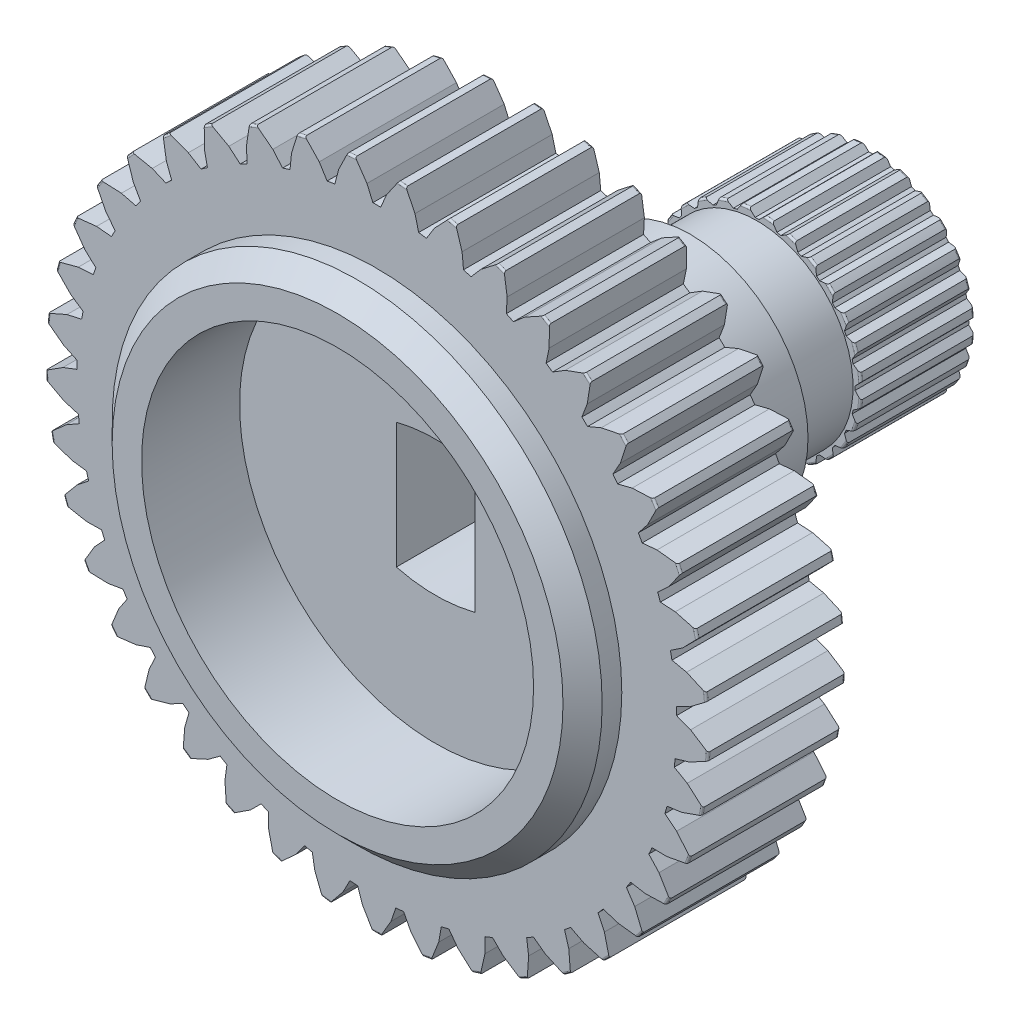
SolidWorks part; units mm, degrees
material "Latón de decoletaje, UNS C36000"
ref_plane "Alzado" through (0, 0, 0) normal (0, 0, 1) x (1, 0, 0)
ref_plane "Planta" through (0, 0, 0) normal (0, 1, 0) x (1, 0, 0)
ref_plane "Vista lateral" through (0, 0, 0) normal (1, 0, 0) x (0, 0, -1)
sketch "Croquis1" plane through (0, 0, 0) normal (0, 0, 1) x (1, 0, 0)
  circle A0 centre (0, 0) radius 8.45
  dimension "D1" = 16.9
extrude "Saliente-Extruir1" add sketch "Croquis1" along normal blind 3.5
fillet "Redondeo1" radius 0.05 2 edges at (8.45, 0, 0) (8.45, 0, 3.5)
sketch "Croquis2" plane through (0, 0, 3.5) normal (0, 0, 1) x (1, 0, 0)
  circle A0 centre (0, 0) radius 6.25
  dimension "D1" = 12.5
extrude "Saliente-Extruir2" add sketch "Croquis2" along normal blind 1
chamfer "Chaflán1" distance 0.5 angle 45 1 edges at (6.25, 0, 4.5)
sketch "Croquis3" plane through (0, 0, 0) normal (0, 0, -1) x (-1, 0, 0)
  line L0 (0, 0) -> (0, 11.5897) construction
  line L1 (0.55, 8.6) -> (-0.55, 8.6)
  line L2 (-0.55, 8.6) -> (-0.55, 8.4321)
  line L3 (-0.55, 8.4321) -> (-0.25, 8)
  line L4 (-0.25, 8) -> (-0.1, 7.6493)
  line L5 (0.25, 8) -> (0.1, 7.6493)
  line L6 (0.55, 8.6) -> (0.55, 8.4321)
  line L7 (0.55, 8.4321) -> (0.25, 8)
  circle A0 centre (0, 0) radius 7.65
  circle A1 centre (0, 0) radius 8.45 construction
  circle A2 centre (0, 0) radius 3.5
  point P16 (0, 8.6)
  circle M6 centre (0, 0) radius 8.4
  dimension "D1" = 15.3
  dimension "D7" = 7
  dimension "D2" = 0.55
  dimension "D3" = 0.1
  dimension "D4" = 8.6
  dimension "D5" = 8
  dimension "D6" = 0.25
extrude "Cortar-Extruir1" cut sketch "Croquis3" against normal blind 3.8 contours L0 A0 L5 L7 M6 | A0 L0 L3 L4 M6 | L0 L1 L2 L3 M6 | L0 L7 L6 L1 M6 region at (0.1687, 8.1144, 0) region at (-0.1687, 8.1144, 0) region at (0.2771, 8.4977, 0) region at (-0.2771, 8.4977, 0)
pattern_circular "MatrizC1" count 41 over 360 about axis through (0, 0, 3.5) along (0, 0, -1) of "Cortar-Extruir1"
extrude "Saliente-Extruir3" add sketch "Croquis3<3>" along normal blind 1.8 contours A2 region at (0, 0, 0)
sketch "Croquis3<3>" plane through (0, 0, 0) normal (0, 0, -1) x (-1, 0, 0) same geometry as "Croquis3"
sketch "Croquis5" plane through (0, 0, -1.8) normal (0, 0, -1) x (-1, 0, 0)
  circle A0 centre (0, 0) radius 3
  dimension "D1" = 6
extrude "Saliente-Extruir4" add sketch "Croquis5" along normal blind 2.7
sketch "Croquis6" plane through (0, 0, -4.5) normal (0, 0, -1) x (-1, 0, 0)
  circle A0 centre (0, 0) radius 2.65
  dimension "D1" = 5.3
extrude "Saliente-Extruir5" add sketch "Croquis6" along normal blind 4.6
sketch "Croquis8" plane through (0, 0, -4.5) normal (0, 0, -1) x (-1, 0, 0)
  circle A0 centre (0, 0) radius 2.45
  dimension "D1" = 4.9
extrude "Cortar-Extruir3" cut sketch "Croquis8" along normal blind 1.7 flip side to cut
fillet "Redondeo4" radius 0.05 2 edges at (-2.65, 0, -9.1) (-2.65, 0, -6.2)
sketch "Croquis7" plane through (0, 0, -9.1) normal (0, 0, -1) x (-1, 0, 0)
  line L0 (0, 0) -> (0, 4.6002) construction
  line L1 (0.2, 2.7) -> (-0.2, 2.7)
  line L2 (-0.2, 2.7) -> (-0.2, 2.6424)
  line L3 (-0.2, 2.6424) -> (-0.12, 2.5662)
  line L4 (-0.12, 2.5662) -> (-0.05, 2.4995)
  line L5 (0.2, 2.7) -> (0.2, 2.6424)
  line L6 (0.2, 2.6424) -> (0.12, 2.5662)
  line L7 (0.12, 2.5662) -> (0.05, 2.4995)
  circle A0 centre (0, 0) radius 2.5
  circle A2 centre (0, 0) radius 2.65 construction
  point P12 (0, 2.7)
  dimension "D1" = 5
  dimension "D3" = 0.05
  dimension "D2" = 0.2
  dimension "D4" = 0.12
  dimension "D5" = 2.7
extrude "Cortar-Extruir2" cut sketch "Croquis7" against normal blind 2.9 contours L0 A0 L7 L6 | L0 L1 L2 | L0 L5 L1 | A0 L0 L3 L4 region at (0, 2.619, -9.1)
pattern_circular "MatrizC2" count 28 over 360 about axis through (0, 0, -9.1) along (0, 0, 1) of "Cortar-Extruir2"
sketch "Croquis9" plane through (0, 0, 0) normal (0, 0, -1) x (-1, 0, 0)
  circle A0 centre (0, 6.3) radius 0.7
  circle A1 centre (0, 0) radius 3.5 construction
  point P2 (0, -3.5)
  point P3 (0, 7)
  dimension "D1" = 1.4
  dimension "D2" = 10.5
extrude "Cortar-Extruir4" cut sketch "Croquis9" against normal blind 1
sketch "Croquis10" plane through (0, 0, -9.1) normal (0, 0, -1) x (-1, 0, 0)
  circle A0 centre (0, 0) radius 1.5
  dimension "D1" = 3
extrude "Cortar-Extruir5" cut sketch "Croquis10" against normal blind 4
chamfer "Chaflán2" distance 0.3 angle 45 1 edges at (-1.5, 0, -9.1)
sketch "Croquis11" plane through (0, 0, 4.5) normal (0, 0, 1) x (1, 0, 0)
  circle A0 centre (0, 0) radius 5
  dimension "D1" = 10
extrude "Cortar-Extruir6" cut sketch "Croquis11" against normal blind 2.5
sketch "Croquis12" plane through (0, 0, 2) normal (0, 0, 1) x (1, 0, 0)
  line L0 (1, 1.6) -> (1, -1.6)
  line L1 (1, -1.6) -> (-1, -1.6) construction
  line L2 (-1, -1.6) -> (-1, 1.6)
  line L3 (-1, 1.6) -> (1, 1.6) construction
  arc A0 (-1, 1.6) -> (1, 1.6) centre (0, -2.273) cw
  arc A1 (1, -1.6) -> (-1, -1.6) centre (0, 2.273) cw
  point P3 (1, 0)
  point P5 (0, 1.6)
  dimension "D3" = 4
  dimension "D1" = 3.2
  dimension "D2" = 2
extrude "Cortar-Extruir7" cut sketch "Croquis12" against normal blind 3
